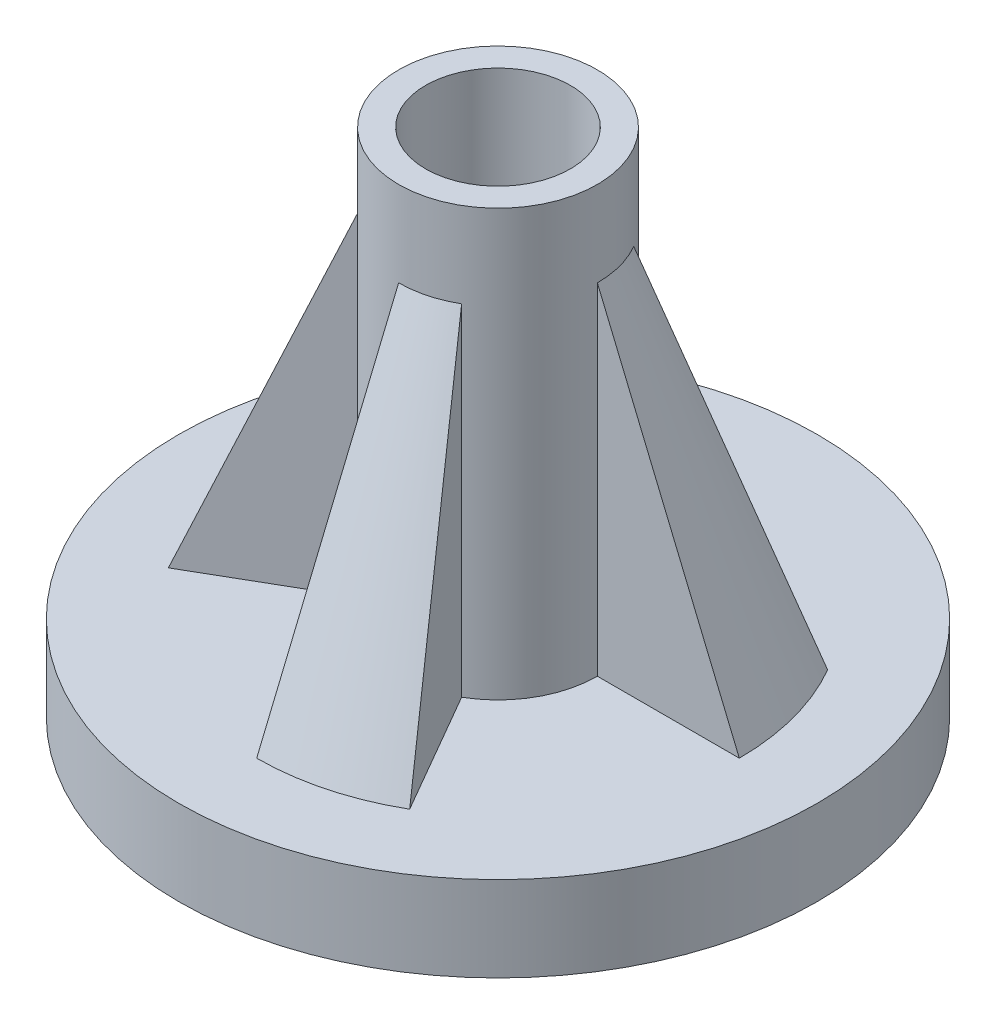
SolidWorks part; units mm, degrees
ref_plane "前视基准面" through (0, 0, 0) normal (0, 0, 1) x (1, 0, 0)
ref_plane "上视基准面" through (0, 0, 0) normal (0, 1, 0) x (1, 0, 0)
ref_plane "右视基准面" through (0, 0, 0) normal (1, 0, 0) x (0, 0, -1)
other "Configuration Table"
sketch "草图1" plane through (0, 0, 0) normal (0, 1, 0) x (1, 0, 0)
  circle A0 centre (0, 0) radius 10.4
  dimension "D1" = 20.8
extrude "凸台-拉伸1" add sketch "草图1" along normal blind 1.8
sketch "草图2" plane through (0, 1.8, 0) normal (0, 1, 0) x (1, 0, 0)
  circle A0 centre (0, 0) radius 11.25
  dimension "D1" = 22.5
extrude "凸台-拉伸2" add sketch "草图2" along normal blind 3
sketch "草图3" plane through (0, 4.8, 0) normal (0, 1, 0) x (1, 0, 0)
  circle A0 centre (0, 0) radius 3.5
  circle A1 centre (0, 0) radius 2.55
  circle A2 centre (0, 0) radius 1.5
  dimension "D1" = 7
  dimension "D2" = 5.1
  dimension "D3" = 3
extrude "凸台-拉伸3" add sketch "草图3" along normal blind 15 contours A0 A1 region at (-3.401, 4.8, 0)
extrude "切除-拉伸2" cut sketch "草图3<4>" against normal up to surface (4.8 mm away) contours A2 up to face at (0, 0, 10.4)
sketch "草图3<4>" plane through (0, 4.8, 0) normal (0, 1, 0) x (1, 0, 0) same geometry as "草图3"
sketch "草图6" plane through (0, 0, 0) normal (1, 0, 0) x (0, 0, -1)
  line L0 (0, 0) -> (0, 11.6571) construction
  line L1 (0, 0) -> (14.4338, 0) construction
  line L2 (3.5, 16.8) -> (8.5, 4.8)
  line L3 (3.5, 4.8) -> (3.5, 19.8) construction
  line L4 (11.25, 4.8) -> (-11.25, 4.8) construction
  line L5 (8.5, 4.8) -> (3.5, 4.8)
  line L6 (3.5, 4.8) -> (3.5, 16.8)
  line L7 (-8.5, 4.8) -> (-3.5, 4.8)
  line L8 (-3.5, 16.8) -> (-8.5, 4.8)
  line L9 (-3.5, 4.8) -> (-3.5, 16.8)
  dimension "D1" = 5
  dimension "D2" = 12
revolve "旋转3" add sketch "草图6" angle 30 about L0 region at (0, 8.8, -5.1667) region at (0, 8.8, 5.1667)
sketch "草图9" plane through (0, 0, 0) normal (0, 0, 1) x (1, 0, 0)
  line L0 (3.5, 4.8) -> (8.5, 4.8)
  line L1 (3.5, 16.8) -> (3.5, 4.8)
  line L2 (8.5, 4.8) -> (3.5, 16.8)
  line L3 (3.5, 4.8) -> (3.5, 19.8) construction
  line L4 (0, 0) -> (0, 22.6974) construction
  line L6 (-8.5, 4.8) -> (-3.5, 16.8)
  line L7 (-3.5, 4.8) -> (-8.5, 4.8)
  line L8 (-3.5, 16.8) -> (-3.5, 4.8)
  dimension "D1" = 5
  dimension "D2" = 12
revolve "旋转4" add sketch "草图9" angle 30 about L4
sketch "草图10" plane through (0, 0, 0) normal (0, -1, 0) x (1, 0, 0)
  line L0 (0, 0) -> (14.3336, 0) construction
  line L1 (0, 0) -> (0, 5.5131) construction
  line L2 (0, 0) -> (10.8585, 0.95)
  line L3 (0, 0) -> (10.8585, -0.95)
  line L4 (0, 0) -> (-0.95, -10.8585)
  line L5 (0, 0) -> (0.95, -10.8585)
  line L6 (0, 0) -> (-10.8585, 0.95)
  line L7 (0, 0) -> (-10.8585, -0.95)
  line L8 (0, 0) -> (0.95, 10.8585)
  line L9 (0, 0) -> (-0.95, 10.8585)
  line L10 (0, 0) -> (10.5286, 2.8211)
  line L11 (0, 0) -> (10.5286, -2.8211)
  line L12 (0, 0) -> (2.8211, -10.5286)
  line L13 (0, 0) -> (-2.8211, -10.5286)
  line L14 (0, 0) -> (-10.5286, -2.8211)
  line L15 (0, 0) -> (-10.5286, 2.8211)
  line L16 (0, 0) -> (-2.8211, 10.5286)
  line L17 (0, 0) -> (2.8211, 10.5286)
  arc A0 (9.6593, 2.5882) -> (9.6593, -2.5882) centre (0, 0) ccw
  arc A1 (10.8585, 0.95) -> (10.8585, -0.95) centre (0, 0) cw
  arc A2 (0.95, -10.8585) -> (-0.95, -10.8585) centre (0, 0) cw
  arc A3 (-10.8585, -0.95) -> (-10.8585, 0.95) centre (0, 0) cw
  arc A4 (-0.95, 10.8585) -> (0.95, 10.8585) centre (0, 0) cw
  circle A5 centre (0, 0) radius 10
  circle A7 centre (0, 0) radius 10.9
  arc A9 (9.9619, 0.8716) -> (9.9619, -0.8716) centre (0, 0) cw
  circle A10 centre (0, 0) radius 9
  arc A11 (10.5286, 2.8211) -> (10.5319, -2.8087) centre (0, 0) cw
  arc A12 (8.6933, 2.3294) -> (8.6933, -2.3294) centre (0, 0) cw
  point P25 (0, 0)
  circle M5 centre (0, 0) radius 10.4
  dimension "D3" = 20
  dimension "D4" = 21.8
  dimension "D5" = 18
  dimension "D1" = 5
  dimension "D6" = 15
  dimension "D2" = 4
  dimension "D7" = 4
extrude "凸台-拉伸4" add sketch "草图10" along normal blind 2 contours A3 L7 L6 M5 | A0 L6 L7 M5 | A10 L6 A0 L7 | A10 L15 A0 L6 | A10 L7 A0 L14 | A10 L9 A0 L16 | A10 L8 A0 L9 | A10 L17 A0 L8 | A0 L8 L9 M5 | A4 L9 L8 M5 | A10 L2 A5 L10 | A10 L3 A5 L2 | A10 L11 A5 L3 | A5 L3 L2 M5 | A1 L2 L3 M5 | A10 L13 A0 L4 | A10 L4 A0 L5 | A10 L5 A0 L12 | A0 L4 L5 M5 | A2 L5 L4 M5 region at (9.3524, 0, 1.6491) region at (9.4967, 0, 0) region at (9.3524, 0, -1.6491) region at (0, 0, -9.4967) region at (-1.6491, 0, -9.3524) region at (1.6491, 0, -9.3524) region at (-9.4967, 0, 0) region at (-9.3524, 0, 1.6491) region at (-9.3524, 0, -1.6491) region at (0, 0, 9.4967) region at (1.6491, 0, 9.3524) region at (-1.6491, 0, 9.3524) region at (10.1884, 0, 0) region at (0, 0, -10.1884) region at (-10.1884, 0, 0) region at (0, 0, 10.1884) region at (10.6384, 0, 0) region at (0, 0, -10.6384) region at (-10.6384, 0, 0) region at (0, 0, 10.6384)
sketch "草图11" plane through (0, 0, 0) normal (0, 0, 1) x (1, 0, 0)
  line L0 (10.9, 0) -> (9.9619, -2)
  line L1 (9.9619, -2) -> (10.9, -2)
  line L2 (10.9, -2) -> (10.9, 0)
  line L3 (0, 0) -> (0, -3.1109) construction
revolve "切除-旋转2" cut sketch "草图11" angle 360 about L3 region at (10.5873, -1.3333, 0)
sketch "草图14" plane through (0, 0, 0) normal (1, 0, 0) x (0, 0, -1)
  line L0 (-2.5783, -2) -> (2.5783, -2) construction
  line L1 (-11.25, 1.8) -> (0, 1.8)
  line L2 (-11.25, 1.8) -> (-11.25, -2)
  line L3 (-11.25, -2) -> (0, -2)
  line L4 (0, 1.8) -> (0, -2)
revolve "切除-旋转3" cut sketch "草图14" angle 360 about L4
